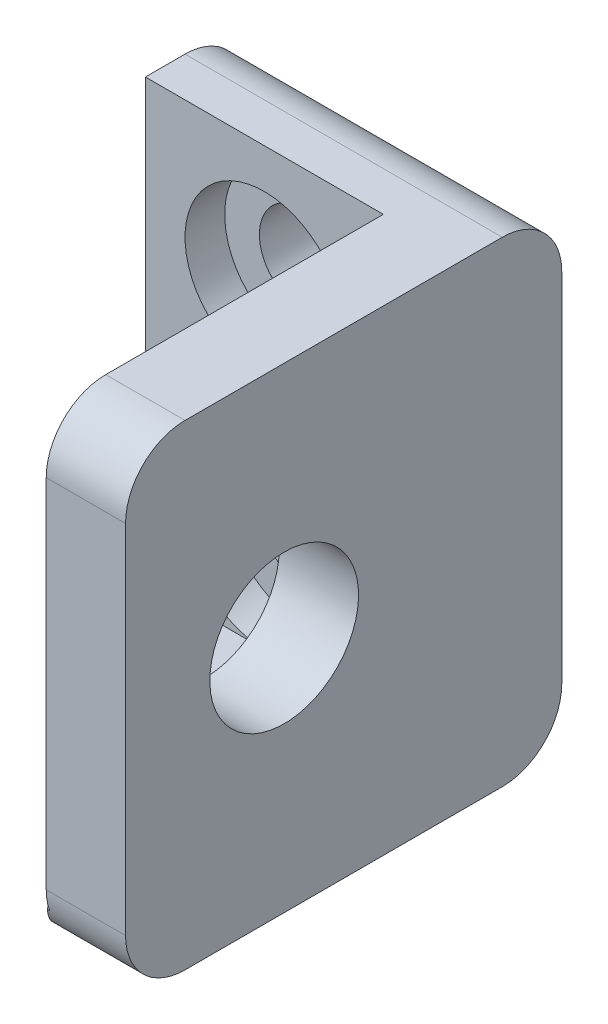
SolidWorks part; units mm, degrees
material "3D printed plastic"
ref_plane "Front Plane" through (0, 0, 0) normal (0, 0, 1) x (1, 0, 0)
ref_plane "Top Plane" through (0, 0, 0) normal (0, 1, 0) x (1, 0, 0)
ref_plane "Right Plane" through (0, 0, 0) normal (1, 0, 0) x (0, 0, -1)
sketch "Sketch1" plane through (0, 0, 0) normal (0, 0, 1) x (1, 0, 0)
  line L0 (-8, 12) -> (8, -12) construction
  line L1 (8, 12) -> (-8, 12)
  line L2 (8, 12) -> (8, -12)
  line L3 (8, -12) -> (-8, -12)
  line L4 (-8, 12) -> (-8, -12)
  line L5 (8, -12) -> (7.5178, -11.8393) construction
  line L6 (-2, -6) -> (-2, 6) construction
  line L7 (-2, 0) -> (0, 0) construction
  circle A0 centre (-2, 6) radius 2.25
  circle A1 centre (-2, -6) radius 2.25
  dimension "D4" = 4.5
  dimension "D1" = 24
  dimension "D2" = 16
  dimension "D3" = 12
  dimension "D5" = 6
extrude "Boss-Extrude1" add sketch "Sketch1" along normal blind 5
sketch "Sketch2" plane through (0, 0, 5) normal (0, 0, 1) x (1, 0, 0)
  line L1 (4, 12) -> (8, 12)
  line L2 (4, 12) -> (4, -12)
  line L3 (4, -12) -> (8, -12)
  line L4 (8, 12) -> (8, -12)
  line L5 (8, 12) -> (-8, 12) construction
  dimension "D1" = 4
  dimension "D2" = 0
extrude "Boss-Extrude2" add sketch "Sketch2" along normal blind 17 and the other way up to surface (5 mm away) other way up to face at (0.25, 6, 0)
sketch "Sketch3" plane through (8, 0, 0) normal (1, 0, 0) x (0, 0, -1)
  line L0 (0, 0) -> (-14, 0) construction
  line L1 (0, -12) -> (0, 12) construction
  line L2 (0, 12) -> (-22, 12) construction
  circle A0 centre (-14, 0) radius 3.75
  dimension "D1" = 7.5
  dimension "D3" = 12
  dimension "D2" = 14
extrude "Cut-Extrude1" cut sketch "Sketch3" against normal through all
sketch "Sketch4" plane through (0, -12, 0) normal (0, -1, 0) x (1, 0, 0)
  line L0 (4, 22) -> (-8, 5)
  line L1 (-8, 5) -> (4, 5)
  line L2 (4, 5) -> (4, 22)
extrude "Boss-Extrude3" add sketch "Sketch4" against normal blind 2
fillet "Fillet1" radius 3 4 edges at (0, 12, 0) (6, 12, 22) (6, -12, 22) (0, -12, 0)
sketch "Sketch5" plane through (0, 0, 5) normal (0, 0, 1) x (1, 0, 0)
  circle A0 centre (-2, 6) radius 4
  circle A1 centre (-2, -6) radius 4
  dimension "D1" = 8
extrude "Cut-Extrude2" cut sketch "Sketch5" against normal blind 2
